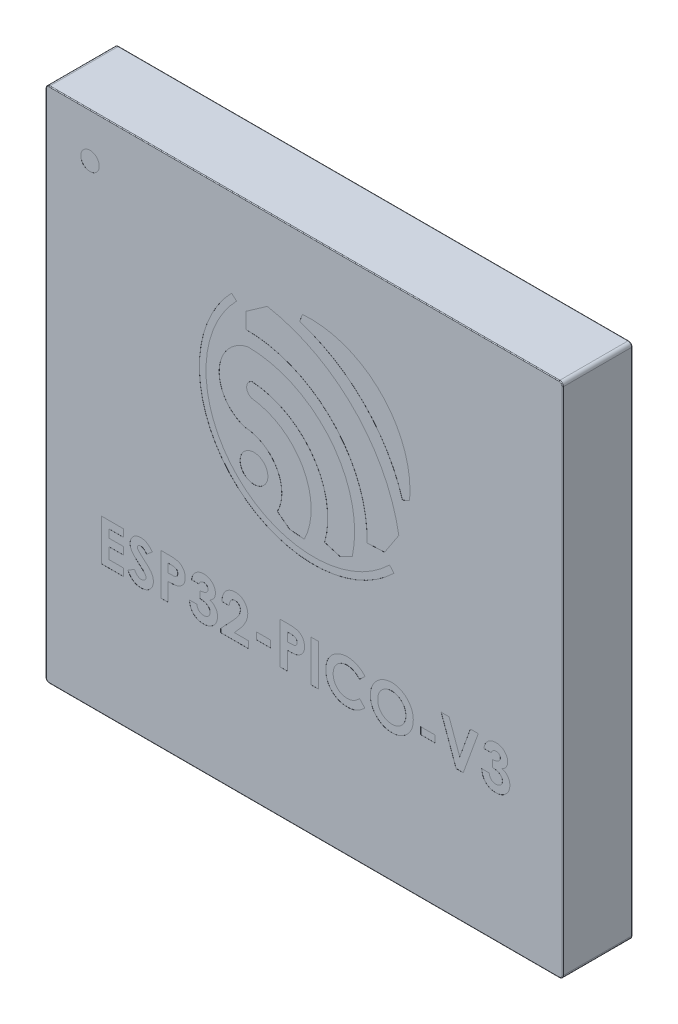
SolidWorks part; units mm, degrees
other "ESP32-PICO-V3-SoC" parameters "D5"=0.3678, "D1"=3.1308, "D2"=3.0402, "D3"=0.4115, "D4"=0.3, "D6"=0.3296, "D7"=0.2637, "D8"=0.9806, "D10"=0.5, "D11"=0.25, "D9"=6
ref_plane "Front Plane" through (0, 0, 0) normal (0, 0, 1) x (1, 0, 0)
ref_plane "Top Plane" through (0, 0, 0) normal (0, 1, 0) x (1, 0, 0)
ref_plane "Right Plane" through (0, 0, 0) normal (1, 0, 0) x (0, 0, -1)
sketch "Sketch1" plane through (0, 0, 0) normal (0, 1, 0) x (1, 0, 0)
  line L1 (-3.5, -3.5) -> (3.5, -3.5)
  line L2 (-3.5, -3.5) -> (-3.5, 3.5)
  line L3 (-3.5, 3.5) -> (3.5, 3.5)
  line L4 (3.5, -3.5) -> (3.5, 3.5)
  line L5 (-3.5, -3.5) -> (3.5, 3.5) construction
  line L6 (-3.5, 3.5) -> (3.5, -3.5) construction
  point P0 (0, 0)
  dimension "D1" = 7
  dimension "D2" = 7
extrude "Boss-Extrude1" add sketch "Sketch1" along normal blind 0.94
fillet "Fillet1" radius 0.05 4 edges at (3.5, 0.47, -3.5) (3.5, 0.47, 3.5) (-3.5, 0.47, 3.5) (-3.5, 0.47, -3.5)
fillet "Fillet2" radius 0.01 16 edges at (3.4854, 0.94, 3.4854) (0, 0.94, 3.5) (-3.4854, 0.94, 3.4854) (-3.5, 0.94, 0) (-3.4854, 0.94, -3.4854) (0, 0.94, -3.5) (3.4854, 0.94, -3.4854) (3.5, 0.94, 0) (3.5, 0, 0) (3.4854, 0, -3.4854) (0, 0, -3.5) (3.4854, 0, 3.4854) (0, 0, 3.5) (-3.4854, 0, 3.4854) (-3.5, 0, 0) (-3.4854, 0, -3.4854)
sketch "Sketch2" plane through (0, 0, 0) normal (0, -1, 0) x (1, 0, 0)
  line L0 (2.175, 2.475) -> (2.475, 2.175)
  line L1 (-2.425, -2.475) -> (2.425, -2.475)
  line L2 (-2.475, -2.425) -> (-2.475, 2.425)
  line L3 (-2.425, 2.475) -> (2.175, 2.475)
  line L4 (2.475, -2.425) -> (2.475, 2.175)
  line L5 (-2.4604, -2.4604) -> (2.475, 2.475) construction
  line L6 (-2.4604, 2.4604) -> (2.4604, -2.4604) construction
  line L7 (2.175, 2.475) -> (2.475, 2.475) construction
  line L8 (2.475, 2.175) -> (2.475, 2.475) construction
  line L9 (-2.475, 2.475) -> (-2.425, 2.475) construction
  line L10 (-2.475, 2.475) -> (-2.4604, 2.4604) construction
  line L11 (-2.475, 2.425) -> (-2.475, 2.475) construction
  line L12 (-2.475, -2.475) -> (-2.475, -2.425) construction
  line L13 (-2.475, -2.475) -> (-2.4604, -2.4604) construction
  line L14 (-2.475, -2.475) -> (-2.425, -2.475) construction
  line L15 (2.475, -2.475) -> (2.475, -2.425) construction
  line L16 (2.4604, -2.4604) -> (2.475, -2.475) construction
  line L17 (2.425, -2.475) -> (2.475, -2.475) construction
  line L18 (0, -1000) -> (0, 49000) construction
  line L23 (-0.375, 3.425) -> (-0.125, 3.425)
  line L24 (-0.375, 3.425) -> (-0.375, 3.025)
  line L25 (-0.375, 3.025) -> (-0.125, 3.025)
  line L26 (-0.125, 3.425) -> (-0.125, 3.025)
  line L27 (-0.375, 3.425) -> (-0.125, 3.025) construction
  line L28 (-0.375, 3.025) -> (-0.125, 3.425) construction
  line L30 (-0.875, 3.425) -> (-0.875, 3.025)
  line L31 (-0.875, 3.425) -> (-0.625, 3.425)
  line L32 (-0.625, 3.425) -> (-0.625, 3.025)
  line L33 (-0.875, 3.025) -> (-0.625, 3.025)
  line L34 (-0.875, 3.025) -> (-0.625, 3.425) construction
  line L35 (-0.875, 3.425) -> (-0.625, 3.025) construction
  line L36 (-1.375, 3.425) -> (-1.375, 3.025)
  line L37 (-1.375, 3.425) -> (-1.125, 3.425)
  line L38 (-1.125, 3.425) -> (-1.125, 3.025)
  line L39 (-1.375, 3.025) -> (-1.125, 3.025)
  line L40 (-1.375, 3.025) -> (-1.125, 3.425) construction
  line L41 (-1.375, 3.425) -> (-1.125, 3.025) construction
  line L42 (-1.875, 3.425) -> (-1.875, 3.025)
  line L43 (-1.875, 3.425) -> (-1.625, 3.425)
  line L44 (-1.625, 3.425) -> (-1.625, 3.025)
  line L45 (-1.875, 3.025) -> (-1.625, 3.025)
  line L46 (-1.875, 3.025) -> (-1.625, 3.425) construction
  line L47 (-1.875, 3.425) -> (-1.625, 3.025) construction
  line L48 (-0.375, 3.425) -> (-0.875, 3.425) construction
  line L49 (-2.375, 3.425) -> (-2.375, 3.025)
  line L66 (-2.375, 3.425) -> (-2.125, 3.425)
  line L162 (-1000, 0) -> (49000, 0) construction
  line L163 (-3.5, 3.5) -> (3.5, 3.5) construction
  line L164 (-2.125, 3.425) -> (-2.125, 3.025)
  line L165 (-2.375, 3.025) -> (-2.125, 3.025)
  line L166 (-2.375, 3.025) -> (-2.125, 3.425) construction
  line L167 (-2.375, 3.425) -> (-2.125, 3.025) construction
  line L168 (-2.875, 3.425) -> (-2.875, 3.025)
  line L169 (-2.875, 3.425) -> (-2.625, 3.425)
  line L170 (-2.625, 3.425) -> (-2.625, 3.025)
  line L171 (-2.875, 3.025) -> (-2.625, 3.025)
  line L172 (-2.875, 3.025) -> (-2.625, 3.425) construction
  line L173 (-2.875, 3.425) -> (-2.625, 3.025) construction
  line L174 (2.875, 3.425) -> (2.625, 3.025) construction
  line L175 (2.875, 3.025) -> (2.625, 3.425) construction
  line L176 (2.375, 3.425) -> (2.125, 3.025) construction
  line L177 (2.375, 3.025) -> (2.125, 3.425) construction
  line L178 (0.375, 3.425) -> (0.875, 3.425) construction
  line L179 (1.875, 3.425) -> (1.625, 3.025) construction
  line L180 (1.875, 3.025) -> (1.625, 3.425) construction
  line L181 (1.375, 3.425) -> (1.125, 3.025) construction
  line L182 (1.375, 3.025) -> (1.125, 3.425) construction
  line L183 (0.875, 3.425) -> (0.625, 3.025) construction
  line L184 (0.875, 3.025) -> (0.625, 3.425) construction
  line L185 (0.375, 3.025) -> (0.125, 3.425) construction
  line L186 (0.375, 3.425) -> (0.125, 3.025) construction
  line L187 (2.875, 3.025) -> (2.625, 3.025)
  line L188 (2.625, 3.425) -> (2.625, 3.025)
  line L189 (2.875, 3.425) -> (2.625, 3.425)
  line L190 (2.875, 3.425) -> (2.875, 3.025)
  line L191 (2.375, 3.025) -> (2.125, 3.025)
  line L192 (2.125, 3.425) -> (2.125, 3.025)
  line L193 (2.375, 3.425) -> (2.125, 3.425)
  line L194 (2.375, 3.425) -> (2.375, 3.025)
  line L195 (1.875, 3.025) -> (1.625, 3.025)
  line L196 (1.625, 3.425) -> (1.625, 3.025)
  line L197 (1.875, 3.425) -> (1.625, 3.425)
  line L198 (1.875, 3.425) -> (1.875, 3.025)
  line L199 (1.375, 3.025) -> (1.125, 3.025)
  line L200 (1.125, 3.425) -> (1.125, 3.025)
  line L201 (1.375, 3.425) -> (1.125, 3.425)
  line L202 (1.375, 3.425) -> (1.375, 3.025)
  line L203 (0.875, 3.025) -> (0.625, 3.025)
  line L204 (0.625, 3.425) -> (0.625, 3.025)
  line L205 (0.875, 3.425) -> (0.625, 3.425)
  line L206 (0.875, 3.425) -> (0.875, 3.025)
  line L207 (0.125, 3.425) -> (0.125, 3.025)
  line L208 (0.375, 3.025) -> (0.125, 3.025)
  line L209 (0.375, 3.425) -> (0.375, 3.025)
  line L210 (0.375, 3.425) -> (0.125, 3.425)
  line L211 (0.375, -3.425) -> (0.125, -3.025) construction
  line L212 (0.375, -3.025) -> (0.125, -3.425) construction
  line L213 (0.875, -3.025) -> (0.625, -3.425) construction
  line L214 (0.875, -3.425) -> (0.625, -3.025) construction
  line L215 (1.375, -3.025) -> (1.125, -3.425) construction
  line L216 (1.375, -3.425) -> (1.125, -3.025) construction
  line L217 (1.875, -3.025) -> (1.625, -3.425) construction
  line L218 (1.875, -3.425) -> (1.625, -3.025) construction
  line L219 (0.375, -3.425) -> (0.875, -3.425) construction
  line L220 (2.375, -3.025) -> (2.125, -3.425) construction
  line L221 (2.375, -3.425) -> (2.125, -3.025) construction
  line L222 (2.875, -3.025) -> (2.625, -3.425) construction
  line L223 (2.875, -3.425) -> (2.625, -3.025) construction
  line L224 (-2.875, -3.425) -> (-2.625, -3.025) construction
  line L225 (-2.875, -3.025) -> (-2.625, -3.425) construction
  line L226 (-2.375, -3.425) -> (-2.125, -3.025) construction
  line L227 (-2.375, -3.025) -> (-2.125, -3.425) construction
  line L228 (-0.375, -3.425) -> (-0.875, -3.425) construction
  line L229 (-1.875, -3.425) -> (-1.625, -3.025) construction
  line L230 (-1.875, -3.025) -> (-1.625, -3.425) construction
  line L231 (-1.375, -3.425) -> (-1.125, -3.025) construction
  line L232 (-1.375, -3.025) -> (-1.125, -3.425) construction
  line L233 (-0.875, -3.425) -> (-0.625, -3.025) construction
  line L234 (-0.875, -3.025) -> (-0.625, -3.425) construction
  line L235 (-0.375, -3.025) -> (-0.125, -3.425) construction
  line L236 (-0.375, -3.425) -> (-0.125, -3.025) construction
  line L237 (0.375, -3.425) -> (0.125, -3.425)
  line L238 (0.375, -3.425) -> (0.375, -3.025)
  line L239 (0.375, -3.025) -> (0.125, -3.025)
  line L240 (0.125, -3.425) -> (0.125, -3.025)
  line L241 (0.875, -3.425) -> (0.875, -3.025)
  line L242 (0.875, -3.425) -> (0.625, -3.425)
  line L243 (0.625, -3.425) -> (0.625, -3.025)
  line L244 (0.875, -3.025) -> (0.625, -3.025)
  line L245 (1.375, -3.425) -> (1.375, -3.025)
  line L246 (1.375, -3.425) -> (1.125, -3.425)
  line L247 (1.125, -3.425) -> (1.125, -3.025)
  line L248 (1.375, -3.025) -> (1.125, -3.025)
  line L249 (1.875, -3.425) -> (1.875, -3.025)
  line L250 (1.875, -3.425) -> (1.625, -3.425)
  line L251 (1.625, -3.425) -> (1.625, -3.025)
  line L252 (1.875, -3.025) -> (1.625, -3.025)
  line L253 (2.375, -3.425) -> (2.375, -3.025)
  line L254 (2.375, -3.425) -> (2.125, -3.425)
  line L255 (2.125, -3.425) -> (2.125, -3.025)
  line L256 (2.375, -3.025) -> (2.125, -3.025)
  line L257 (2.875, -3.425) -> (2.875, -3.025)
  line L258 (2.875, -3.425) -> (2.625, -3.425)
  line L259 (2.625, -3.425) -> (2.625, -3.025)
  line L260 (2.875, -3.025) -> (2.625, -3.025)
  line L261 (-2.875, -3.025) -> (-2.625, -3.025)
  line L262 (-2.625, -3.425) -> (-2.625, -3.025)
  line L263 (-2.875, -3.425) -> (-2.625, -3.425)
  line L264 (-2.875, -3.425) -> (-2.875, -3.025)
  line L265 (-2.375, -3.025) -> (-2.125, -3.025)
  line L266 (-2.125, -3.425) -> (-2.125, -3.025)
  line L267 (-2.375, -3.425) -> (-2.125, -3.425)
  line L268 (-2.375, -3.425) -> (-2.375, -3.025)
  line L269 (-1.875, -3.025) -> (-1.625, -3.025)
  line L270 (-1.625, -3.425) -> (-1.625, -3.025)
  line L271 (-1.875, -3.425) -> (-1.625, -3.425)
  line L272 (-1.875, -3.425) -> (-1.875, -3.025)
  line L273 (-1.375, -3.025) -> (-1.125, -3.025)
  line L274 (-1.125, -3.425) -> (-1.125, -3.025)
  line L275 (-1.375, -3.425) -> (-1.125, -3.425)
  line L276 (-1.375, -3.425) -> (-1.375, -3.025)
  line L277 (-0.875, -3.025) -> (-0.625, -3.025)
  line L278 (-0.625, -3.425) -> (-0.625, -3.025)
  line L279 (-0.875, -3.425) -> (-0.625, -3.425)
  line L280 (-0.875, -3.425) -> (-0.875, -3.025)
  line L281 (-0.125, -3.425) -> (-0.125, -3.025)
  line L282 (-0.375, -3.025) -> (-0.125, -3.025)
  line L283 (-0.375, -3.425) -> (-0.375, -3.025)
  line L284 (-0.375, -3.425) -> (-0.125, -3.425)
  line L285 (3.425, 0.375) -> (3.025, 0.125) construction
  line L286 (3.025, 0.375) -> (3.425, 0.125) construction
  line L287 (3.025, 0.875) -> (3.425, 0.625) construction
  line L288 (3.425, 0.875) -> (3.025, 0.625) construction
  line L289 (3.025, 1.375) -> (3.425, 1.125) construction
  line L290 (3.425, 1.375) -> (3.025, 1.125) construction
  line L291 (3.025, 1.875) -> (3.425, 1.625) construction
  line L292 (3.425, 1.875) -> (3.025, 1.625) construction
  line L293 (3.425, 0.375) -> (3.425, 0.875) construction
  line L294 (3.025, 2.375) -> (3.425, 2.125) construction
  line L295 (3.425, 2.375) -> (3.025, 2.125) construction
  line L296 (3.025, 2.875) -> (3.425, 2.625) construction
  line L297 (3.425, 2.875) -> (3.025, 2.625) construction
  line L298 (3.425, -2.875) -> (3.025, -2.625) construction
  line L299 (3.025, -2.875) -> (3.425, -2.625) construction
  line L300 (3.425, -2.375) -> (3.025, -2.125) construction
  line L301 (3.025, -2.375) -> (3.425, -2.125) construction
  line L302 (3.425, -0.375) -> (3.425, -0.875) construction
  line L303 (3.425, -1.875) -> (3.025, -1.625) construction
  line L304 (3.025, -1.875) -> (3.425, -1.625) construction
  line L305 (3.425, -1.375) -> (3.025, -1.125) construction
  line L306 (3.025, -1.375) -> (3.425, -1.125) construction
  line L307 (3.425, -0.875) -> (3.025, -0.625) construction
  line L308 (3.025, -0.875) -> (3.425, -0.625) construction
  line L309 (3.025, -0.375) -> (3.425, -0.125) construction
  line L310 (3.425, -0.375) -> (3.025, -0.125) construction
  line L311 (3.425, 0.375) -> (3.425, 0.125)
  line L312 (3.425, 0.375) -> (3.025, 0.375)
  line L313 (3.025, 0.375) -> (3.025, 0.125)
  line L314 (3.425, 0.125) -> (3.025, 0.125)
  line L315 (3.425, 0.875) -> (3.025, 0.875)
  line L316 (3.425, 0.875) -> (3.425, 0.625)
  line L317 (3.425, 0.625) -> (3.025, 0.625)
  line L318 (3.025, 0.875) -> (3.025, 0.625)
  line L319 (3.425, 1.375) -> (3.025, 1.375)
  line L320 (3.425, 1.375) -> (3.425, 1.125)
  line L321 (3.425, 1.125) -> (3.025, 1.125)
  line L322 (3.025, 1.375) -> (3.025, 1.125)
  line L323 (3.425, 1.875) -> (3.025, 1.875)
  line L324 (3.425, 1.875) -> (3.425, 1.625)
  line L325 (3.425, 1.625) -> (3.025, 1.625)
  line L326 (3.025, 1.875) -> (3.025, 1.625)
  line L327 (3.425, 2.375) -> (3.025, 2.375)
  line L328 (3.425, 2.375) -> (3.425, 2.125)
  line L329 (3.425, 2.125) -> (3.025, 2.125)
  line L330 (3.025, 2.375) -> (3.025, 2.125)
  line L331 (3.425, 2.875) -> (3.025, 2.875)
  line L332 (3.425, 2.875) -> (3.425, 2.625)
  line L333 (3.425, 2.625) -> (3.025, 2.625)
  line L334 (3.025, 2.875) -> (3.025, 2.625)
  line L335 (3.025, -2.875) -> (3.025, -2.625)
  line L336 (3.425, -2.625) -> (3.025, -2.625)
  line L337 (3.425, -2.875) -> (3.425, -2.625)
  line L338 (3.425, -2.875) -> (3.025, -2.875)
  line L339 (3.025, -2.375) -> (3.025, -2.125)
  line L340 (3.425, -2.125) -> (3.025, -2.125)
  line L341 (3.425, -2.375) -> (3.425, -2.125)
  line L342 (3.425, -2.375) -> (3.025, -2.375)
  line L343 (3.025, -1.875) -> (3.025, -1.625)
  line L344 (3.425, -1.625) -> (3.025, -1.625)
  line L345 (3.425, -1.875) -> (3.425, -1.625)
  line L346 (3.425, -1.875) -> (3.025, -1.875)
  line L347 (3.025, -1.375) -> (3.025, -1.125)
  line L348 (3.425, -1.125) -> (3.025, -1.125)
  line L349 (3.425, -1.375) -> (3.425, -1.125)
  line L350 (3.425, -1.375) -> (3.025, -1.375)
  line L351 (3.025, -0.875) -> (3.025, -0.625)
  line L352 (3.425, -0.625) -> (3.025, -0.625)
  line L353 (3.425, -0.875) -> (3.425, -0.625)
  line L354 (3.425, -0.875) -> (3.025, -0.875)
  line L355 (3.425, -0.125) -> (3.025, -0.125)
  line L356 (3.025, -0.375) -> (3.025, -0.125)
  line L357 (3.425, -0.375) -> (3.025, -0.375)
  line L358 (3.425, -0.375) -> (3.425, -0.125)
  line L359 (-3.425, -0.375) -> (-3.025, -0.125) construction
  line L360 (-3.025, -0.375) -> (-3.425, -0.125) construction
  line L361 (-3.025, -0.875) -> (-3.425, -0.625) construction
  line L362 (-3.425, -0.875) -> (-3.025, -0.625) construction
  line L363 (-3.025, -1.375) -> (-3.425, -1.125) construction
  line L364 (-3.425, -1.375) -> (-3.025, -1.125) construction
  line L365 (-3.025, -1.875) -> (-3.425, -1.625) construction
  line L366 (-3.425, -1.875) -> (-3.025, -1.625) construction
  line L367 (-3.425, -0.375) -> (-3.425, -0.875) construction
  line L368 (-3.025, -2.375) -> (-3.425, -2.125) construction
  line L369 (-3.425, -2.375) -> (-3.025, -2.125) construction
  line L370 (-3.025, -2.875) -> (-3.425, -2.625) construction
  line L371 (-3.425, -2.875) -> (-3.025, -2.625) construction
  line L372 (-3.425, 2.875) -> (-3.025, 2.625) construction
  line L373 (-3.025, 2.875) -> (-3.425, 2.625) construction
  line L374 (-3.425, 2.375) -> (-3.025, 2.125) construction
  line L375 (-3.025, 2.375) -> (-3.425, 2.125) construction
  line L376 (-3.425, 0.375) -> (-3.425, 0.875) construction
  line L377 (-3.425, 1.875) -> (-3.025, 1.625) construction
  line L378 (-3.025, 1.875) -> (-3.425, 1.625) construction
  line L379 (-3.425, 1.375) -> (-3.025, 1.125) construction
  line L380 (-3.025, 1.375) -> (-3.425, 1.125) construction
  line L381 (-3.425, 0.875) -> (-3.025, 0.625) construction
  line L382 (-3.025, 0.875) -> (-3.425, 0.625) construction
  line L383 (-3.025, 0.375) -> (-3.425, 0.125) construction
  line L384 (-3.425, 0.375) -> (-3.025, 0.125) construction
  line L385 (-3.425, -0.375) -> (-3.425, -0.125)
  line L386 (-3.425, -0.375) -> (-3.025, -0.375)
  line L387 (-3.025, -0.375) -> (-3.025, -0.125)
  line L388 (-3.425, -0.125) -> (-3.025, -0.125)
  line L389 (-3.425, -0.875) -> (-3.025, -0.875)
  line L390 (-3.425, -0.875) -> (-3.425, -0.625)
  line L391 (-3.425, -0.625) -> (-3.025, -0.625)
  line L392 (-3.025, -0.875) -> (-3.025, -0.625)
  line L393 (-3.425, -1.375) -> (-3.025, -1.375)
  line L394 (-3.425, -1.375) -> (-3.425, -1.125)
  line L395 (-3.425, -1.125) -> (-3.025, -1.125)
  line L396 (-3.025, -1.375) -> (-3.025, -1.125)
  line L397 (-3.425, -1.875) -> (-3.025, -1.875)
  line L398 (-3.425, -1.875) -> (-3.425, -1.625)
  line L399 (-3.425, -1.625) -> (-3.025, -1.625)
  line L400 (-3.025, -1.875) -> (-3.025, -1.625)
  line L401 (-3.425, -2.375) -> (-3.025, -2.375)
  line L402 (-3.425, -2.375) -> (-3.425, -2.125)
  line L403 (-3.425, -2.125) -> (-3.025, -2.125)
  line L404 (-3.025, -2.375) -> (-3.025, -2.125)
  line L405 (-3.425, -2.875) -> (-3.025, -2.875)
  line L406 (-3.425, -2.875) -> (-3.425, -2.625)
  line L407 (-3.425, -2.625) -> (-3.025, -2.625)
  line L408 (-3.025, -2.875) -> (-3.025, -2.625)
  line L409 (-3.025, 2.875) -> (-3.025, 2.625)
  line L410 (-3.425, 2.625) -> (-3.025, 2.625)
  line L411 (-3.425, 2.875) -> (-3.425, 2.625)
  line L412 (-3.425, 2.875) -> (-3.025, 2.875)
  line L413 (-3.025, 2.375) -> (-3.025, 2.125)
  line L414 (-3.425, 2.125) -> (-3.025, 2.125)
  line L415 (-3.425, 2.375) -> (-3.425, 2.125)
  line L416 (-3.425, 2.375) -> (-3.025, 2.375)
  line L417 (-3.025, 1.875) -> (-3.025, 1.625)
  line L418 (-3.425, 1.625) -> (-3.025, 1.625)
  line L419 (-3.425, 1.875) -> (-3.425, 1.625)
  line L420 (-3.425, 1.875) -> (-3.025, 1.875)
  line L421 (-3.025, 1.375) -> (-3.025, 1.125)
  line L422 (-3.425, 1.125) -> (-3.025, 1.125)
  line L423 (-3.425, 1.375) -> (-3.425, 1.125)
  line L424 (-3.425, 1.375) -> (-3.025, 1.375)
  line L425 (-3.025, 0.875) -> (-3.025, 0.625)
  line L426 (-3.425, 0.625) -> (-3.025, 0.625)
  line L427 (-3.425, 0.875) -> (-3.425, 0.625)
  line L428 (-3.425, 0.875) -> (-3.025, 0.875)
  line L429 (-3.425, 0.125) -> (-3.025, 0.125)
  line L430 (-3.025, 0.375) -> (-3.025, 0.125)
  line L431 (-3.425, 0.375) -> (-3.025, 0.375)
  line L432 (-3.425, 0.375) -> (-3.425, 0.125)
  arc A0 (-2.425, 2.475) -> (-2.475, 2.425) centre (-2.425, 2.425) ccw
  arc A1 (-2.475, -2.425) -> (-2.425, -2.475) centre (-2.425, -2.425) ccw
  arc A2 (2.425, -2.475) -> (2.475, -2.425) centre (2.425, -2.425) ccw
  point P0 (0, 0)
  point P12 (-0.25, 3.225)
  point P76 (0.25, 3.225)
  point P125 (0.25, -3.225)
  point P126 (-0.25, -3.225)
  point P175 (3.225, 0.25)
  point P176 (3.225, -0.25)
  point P225 (-3.225, -0.25)
  point P226 (-3.225, 0.25)
  dimension "D5" = 0.1
  dimension "D1" = 4.95
  dimension "D2" = 4.95
  dimension "D4" = 45
  dimension "D6" = 0.4
  dimension "D7" = 0.25
  dimension "D8" = 0.25
  dimension "D11" = 0.075
  dimension "D3" = 0.3
extrude "Boss-Extrude2" add sketch "Sketch2" along normal blind 0.025
sketch "Sketch3" plane through (0, 0.94, 0) normal (0, 1, 0) x (1, 0, 0)
  line L7 (-3.5, 1.745) -> (3.5, 1.745) construction
  line L8 (-3.5, 3.5) -> (-3.5, -3.5) construction
  line L9 (3.45, -3.5) -> (-3.45, -3.5) construction
  line L10 (-1.3291, -1.0385) -> (-1.4257, -1.0797)
  line L11 (3.5, 3.45) -> (3.5, -3.45) construction
  line L24 (0, 0) -> (0, 3.49) construction
  line L25 (3.45, 3.49) -> (-3.45, 3.49) construction
  line L26 (0.0255, -2.5384) -> (0.0624, -2.4357)
  line L27 (-0.849, -0.2967) -> (-1.0872, -0.3069)
  line L28 (-1.0872, -0.3069) -> (-1.2797, -0.6007)
  line L29 (0.5009, -2.3949) -> (0.7899, -2.1921)
  line L30 (0.7899, -2.1921) -> (0.7899, -1.9791)
  line L31 (0.9165, -2.2488) -> (0.9838, -2.3084)
  line L32 (-1.2141, -0.1242) -> (-1.1542, -0.1913)
  line L33 (0.3643, -0.0586) -> (0.1985, 0.0668)
  line L34 (0.1985, 0.0668) -> (-0.0005, 0.0844)
  line L35 (-0.2752, -0.0172) -> (-0.4855, 0.0454)
  line L36 (-0.4855, 0.0454) -> (-0.6494, -0.0366)
  circle A10 centre (2.9, -2.9) radius 0.125
  arc A24 (-1.3291, -1.0385) -> (0.0624, -2.4357) centre (0.6805, -0.4288) ccw
  arc A25 (-1.2797, -0.6007) -> (0.5009, -2.3949) centre (0.8931, -0.225) ccw
  arc A26 (0.7658, -1.7891) -> (0.8071, -0.8273) centre (0.6531, -1.3025) ccw
  arc A27 (0.9838, -2.3084) -> (-1.2141, -0.1242) centre (-0.1293, -1.2306) ccw
  circle A28 centre (0.6805, -0.4056) radius 0.1881
  arc A29 (-0.2752, -0.0172) -> (0.7055, -1.4089) centre (0.7748, -0.3187) ccw
  arc A30 (0.3643, -0.0586) -> (0.8071, -0.8273) centre (0.8295, -0.3025) ccw
  arc A31 (-0.0005, 0.0844) -> (0.7092, -1.2114) centre (0.8094, -0.3143) ccw
  arc A32 (-0.6494, -0.0366) -> (0.7658, -1.7891) centre (0.7663, -0.3411) ccw
  arc A33 (0.9165, -2.2488) -> (-1.1542, -0.1913) centre (-0.1293, -1.2306) ccw
  arc A34 (-0.849, -0.2967) -> (0.7899, -1.9791) centre (0.7883, -0.3412) ccw
  arc A35 (0.7092, -1.2114) -> (0.7055, -1.4089) centre (0.676, -1.3096) cw
  arc A36 (-1.4257, -1.0797) -> (0.0255, -2.5384) centre (-0.0858, -1.1979) ccw
  text T0 "ESP32-PICO-V3" font "Century Gothic" height 0.56
  point P53 (0, 1.745)
  dimension "D2" = 0.25
  dimension "D3" = 0.6
  dimension "D4" = 0.6
extrude "Cut-Extrude1" cut sketch "Sketch3" against normal blind 0.001
move or copy body "Body-Move/Copy1" bodies to move or copy 131 copy no rotation origin (0, 0, 0) rotation axis (0, 0.7071, 0.7071) rotation angle 180
move or copy body "Body-Move/Copy2" bodies to move or copy 132 copy no translate (0, 0, 0.025)
equation "\"D8@Sketch2\"=\"D10@Sketch2\"/2"
equation "\"D1@Sketch1\"=\"D2@Sketch1\""
equation "\"D1@Sketch2\"=\"D2@Sketch2\""
equation "\"D4@Sketch3\"=\"D3@Sketch3\""
